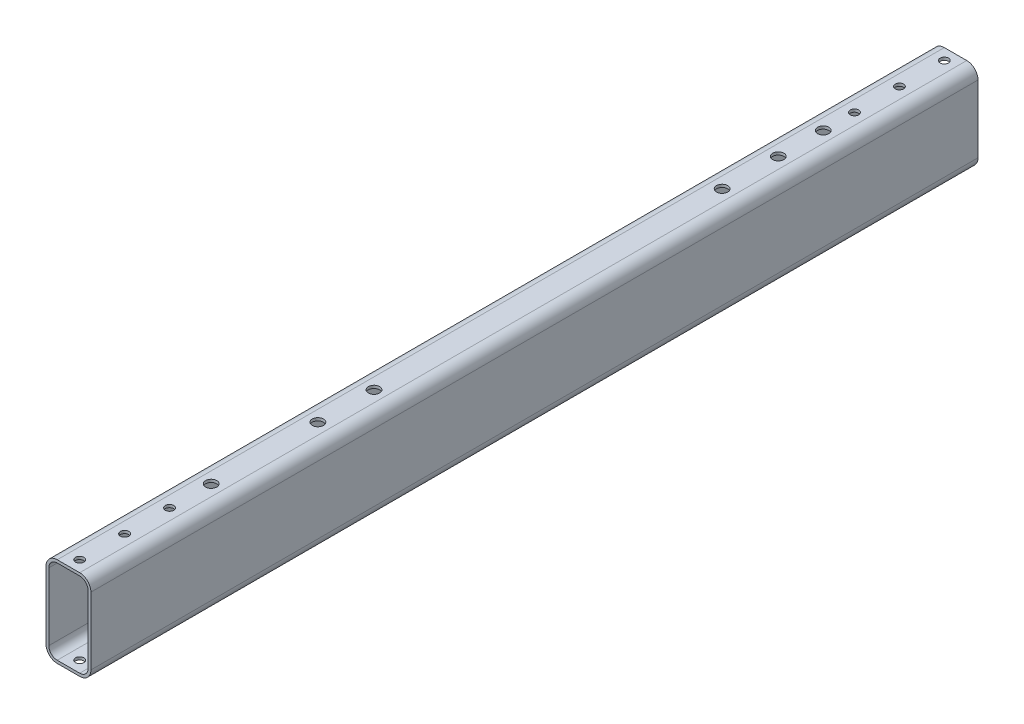
SolidWorks part; units mm, degrees
material "6061-T6 (SS)"
ref_plane "Front Plane" through (0, 0, 0) normal (0, 0, 1) x (1, 0, 0)
ref_plane "Top Plane" through (0, 0, 0) normal (0, 1, 0) x (1, 0, 0)
ref_plane "Right Plane" through (0, 0, 0) normal (1, 0, 0) x (0, 0, -1)
sketch "Sketch1" plane through (0, 0, 0) normal (0, 0, 1) x (1, 0, 0)
  line L1 (-6.35, -25.4) -> (6.35, -25.4)
  line L2 (-12.7, -19.05) -> (-12.7, 19.05)
  line L3 (-6.35, 25.4) -> (6.35, 25.4)
  line L4 (12.7, -19.05) -> (12.7, 19.05)
  line L5 (-12.7, -25.4) -> (12.7, 25.4) construction
  line L6 (-12.7, 25.4) -> (12.7, -25.4) construction
  arc A0 (-12.7, -19.05) -> (-6.35, -25.4) centre (-6.35, -19.05) ccw
  arc A1 (6.35, -25.4) -> (12.7, -19.05) centre (6.35, -19.05) ccw
  arc A2 (6.35, 25.4) -> (12.7, 19.05) centre (6.35, 19.05) cw
  arc A3 (-12.7, 19.05) -> (-6.35, 25.4) centre (-6.35, 19.05) cw
  point P0 (0, 0)
  dimension "D3" = 6.35
  dimension "D1" = 50.8
  dimension "D2" = 25.4
extrude "Extrude-Thin1" add sketch "Sketch1" along normal blind 501.65 thin thin type one direction reverse wall 1.5875
hole_wizard "3/16 (0.1875) Diameter Hole1" positions "3DSketch1" profile "Sketch3" hole size "3/16" standard "ANSI Inch" end condition through all
sketch3d "3DSketch1"
  line L1 (6.35, 25.4, 0) -> (-6.35, 25.4, 0) construction
  line L6 (0, 25.4, 501.65) -> (0, 25.4, 0) construction
  line L7 (6.35, 25.4, 501.65) -> (-6.35, 25.4, 501.65) construction
  point P57 (0, 25.4, 6.35)
  point P59 (0, 25.4, 31.75)
  point P61 (0, 25.4, 57.15)
  point P63 (0, 25.4, 469.9)
  point P65 (0, 25.4, 444.5)
  point P67 (0, 25.4, 495.3)
  dimension "D1" = 25.4
  dimension "D2" = 25.4
  dimension "D3" = 6.35
  dimension "D4" = 25.4
  dimension "D5" = 25.4
  dimension "D6" = 6.35
sketch "Sketch3" plane through (0, 25.4, 495.3) normal (1, 0, 0) x (0, 0, 1)
  line L0 (0, 0) -> (0, 50.8)
  line L1 (0, 50.8) -> (2.3812, 50.8)
  line L2 (2.3812, 50.8) -> (2.3812, 0)
  line L5 (2.3812, 0) -> (0, 0)
  line L11 (0, -6.35) -> (0, 107.95) construction
  dimension "Thru Hole Dia." = 4.7625
  dimension "Thru Hole Depth" = 50.8
hole_wizard "3/16 (0.195) Diameter Hole1" positions "Sketch4" profile "Sketch5" hole size "3/16" standard "ANSI Inch" end condition up to next
sketch "Sketch4" plane through (0, -25.4, 0) normal (0, -1, 0) x (-1, 0, 0)
  point P28 (3.175, -81.2609)
  point P31 (-3.175, -106.6609)
  point P34 (3.175, -132.0609)
  point P37 (-3.175, -157.4609)
  point P40 (3.175, -182.8609)
  point P43 (3.175, -335.2609)
  point P46 (-3.175, -360.6609)
  point P49 (3.175, -386.0609)
  point P52 (-3.175, -411.4609)
  point P60 (-3.175, -208.2609)
  point P63 (3.175, -233.6609)
  point P66 (-3.175, -259.0609)
  point P69 (3.175, -284.4609)
  point P72 (-3.175, -309.8609)
sketch "Sketch5" plane through (-3.175, -25.4, 81.2609) normal (1, 0, 0) x (0, 0, -1)
  line L0 (0, 0) -> (0, 1.5875)
  line L1 (0, 1.5875) -> (2.4765, 1.5875)
  line L2 (2.4765, 1.5875) -> (2.4765, 0)
  line L5 (2.4765, 0) -> (0, 0)
  line L11 (0, -6.35) -> (0, 107.95) construction
  dimension "Thru Hole Dia." = 4.953
  dimension "Thru Hole Depth" = 1.5875
hole_wizard "1/4 (0.25) Diameter Hole1" positions "Sketch7" profile "Sketch6" hole size "1/4" standard "ANSI Inch"
sketch "Sketch7" plane through (0, 25.4, 0) normal (0, 1, 0) x (1, 0, 0)
  point P0 (0, -100.2359)
  point P3 (0, -131.9859)
  point P6 (0, -74.8359)
  point P9 (0, -420.9388)
  point P12 (0, -360.6108)
  point P15 (0, -328.8608)
sketch "Sketch6" plane through (0, 25.4, 100.2359) normal (1, 0, 0) x (0, 0, 1)
  line L0 (0, 0) -> (0, 27.3077)
  line L1 (0, 27.3077) -> (3.175, 25.4)
  line L2 (3.175, 25.4) -> (3.175, 0)
  line L5 (3.175, 0) -> (0, 0)
  line L10 (0, 27.3077) -> (-3.175, 25.4) construction
  line L11 (0, -6.35) -> (0, 107.95) construction
  dimension "Hole Dia." = 6.35
  dimension "Hole Depth" = 25.4
  dimension "Drill Angle" = 118
